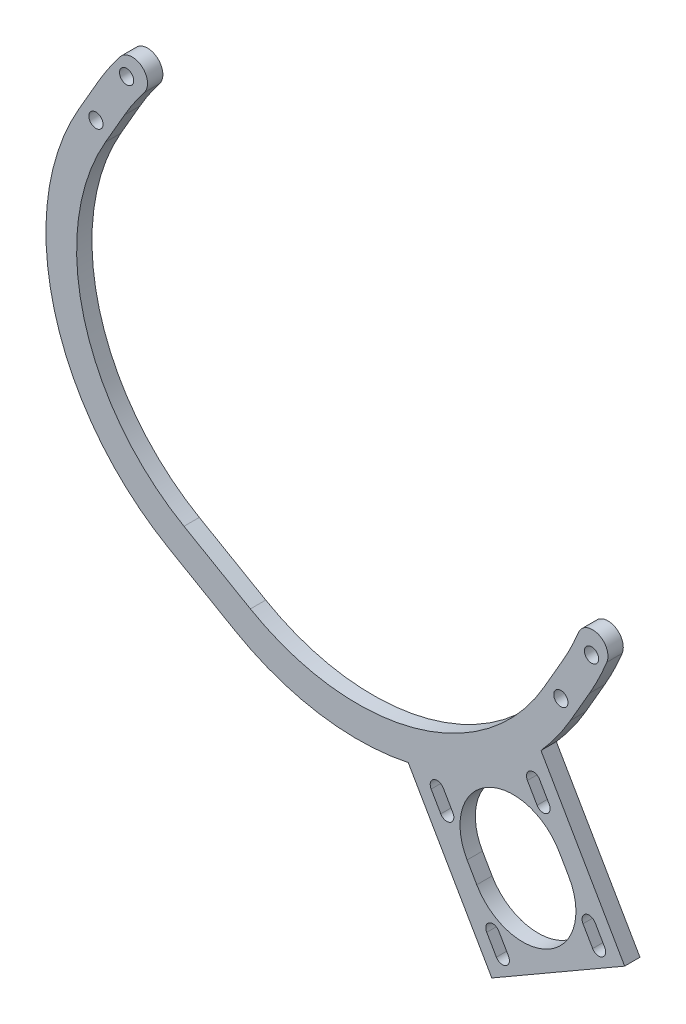
SolidWorks part; units mm, degrees
ref_plane "Front Plane" through (0, 0, 0) normal (0, 0, 1) x (1, 0, 0)
ref_plane "Top Plane" through (0, 0, 0) normal (0, 1, 0) x (1, 0, 0)
ref_plane "Right Plane" through (0, 0, 0) normal (1, 0, 0) x (0, 0, -1)
sketch "Sketch1" plane through (0, 0, -14.157) normal (0, 0, -1) x (-1, 0, 0)
  line L0 (-49.1723, -34.5021) -> (-53.1411, -27.628)
  line L1 (-2.2729, 1.7407) -> (29.3872, -53.0962) construction
  line L2 (20.2218, -53.0962) -> (27.0959, -49.1274)
  line L3 (33.9699, -45.1587) -> (20.2218, -53.0962) construction
  line L4 (17.0468, -47.5969) -> (23.9209, -43.6282)
  line L5 (-43.6731, -31.3271) -> (-47.6418, -24.453)
  line L6 (47.0648, 21.0604) -> (43.096, 27.9345)
  line L7 (30.7949, -39.6594) -> (23.9209, -43.6282)
  line L8 (33.9699, -45.1587) -> (27.0959, -49.1274)
  line L9 (52.564, 24.2354) -> (48.5953, 31.1095)
  arc A0 (-53.1411, -27.628) -> (-56.7299, -20.2712) centre (-2.2729, 1.7407) cw
  arc A3 (-61.0104, 1.7407) -> (-53.1411, -27.628) centre (-2.2729, 1.7407) ccw construction
  circle A4 centre (-53.5664, -20.5413) radius 1.1303 construction
  arc A5 (-49.1723, -34.5021) -> (20.2218, -53.0962) centre (-5.1782, -9.1021) ccw
  arc A6 (-43.6731, -31.3271) -> (17.0468, -47.5969) centre (-5.1782, -9.1021) ccw
  arc A7 (-47.6418, -24.453) -> (-50.8427, -17.8916) centre (-2.2729, 1.7407) cw
  arc A8 (-56.7299, -20.2712) -> (-50.8427, -17.8916) centre (-53.7863, -19.0814) cw
  arc A9 (44.0185, 37.8959) -> (39.014, 33.9872) centre (41.5163, 35.9416) ccw
  arc A10 (43.096, 27.9345) -> (39.014, 33.9872) centre (-2.2729, 1.7407) ccw
  arc A11 (47.0648, 21.0604) -> (30.7949, -39.6594) centre (8.5699, -1.1646) cw
  arc A12 (52.564, 24.2354) -> (33.9699, -45.1587) centre (8.5699, -1.1646) cw
  arc A13 (48.5953, 31.1095) -> (44.0185, 37.8959) centre (-2.2729, 1.7407) ccw
  dimension "D1" = 3.175
  dimension "D2" = 6.35
extrude "Boss-Extrude1" add sketch "Sketch1" along normal blind 3.175
hole_wizard "#4 Clearance Hole1" positions "Sketch5" profile "Sketch4" hole size "#4" standard "Ansi Inch" end condition through all
sketch "Sketch5" plane through (0, 0, -17.332) normal (0, 0, -1) x (-1, 0, 0)
  circle A1 centre (-53.5664, -20.5413) radius 1.1303 construction
  circle A2 centre (49.0206, 24.0227) radius 1.1303 construction
  point P0 (-53.5664, -20.5413)
  point P5 (-47.2164, -31.5398)
  point P8 (42.6706, 35.0212)
  point P11 (49.0206, 24.0227)
sketch "Sketch4" plane through (53.5664, -20.5413, -17.332) normal (1, 0, 0) x (0, 1, 0)
  line L0 (0, 0) -> (0, 3.175)
  line L1 (0, 3.175) -> (1.4732, 3.175)
  line L2 (1.4732, 3.175) -> (1.4732, 0)
  line L3 (-13.9608, 3.175) -> (-39.3608, 3.175) construction
  line L5 (1.4732, 0) -> (0, 0)
  line L11 (0, -6.35) -> (0, 107.95) construction
  dimension "Thru Hole Dia." = 2.9464
  dimension "Thru Hole Depth" = 3.175
ref_plane "Plane1" through (0, -58.42, 0) normal (0, 1, 0) x (-1, 0, 0)
ref_plane "Plane2" through (0, 0, -14.157) normal (0, 0, 1) x (1, 0, 0)
ref_axis "Axis2" through (-65.1865, 0, -14.157) along (1, 0, 0)
ref_axis "Axis3" through (0, 0, -25.4783) along (0, 0, 1)
ref_point "Point1"
ref_axis "Axis4" through (0, -70.9509, -14.157) along (0, 1, 0)
sketch "Sketch6" plane through (0, 0, -14.157) normal (0, 0, 1) x (1, 0, 0)
  line L0 (0, 0) -> (37.0667, -64.2014) construction
  line L1 (0, -70.9509) -> (0, 0.8498) construction
  line L10 (60.4207, -72.9016) -> (32.9243, -88.7766)
  line L15 (60.4207, -72.9016) -> (41.209, -39.6261)
  line L16 (32.9243, -88.7766) -> (13.7127, -55.5011)
  line L17 (41.209, -39.6261) -> (13.7127, -55.5011)
  line L18 (60.4207, -72.9016) -> (13.7127, -55.5011) construction
  line L19 (32.9243, -88.7766) -> (41.209, -39.6261) construction
  line L20 (37.338, -64.6713) -> (39.3319, -68.1248) construction
  line L21 (46.8627, -59.1722) -> (48.8566, -62.6257)
  line L22 (27.8133, -70.1704) -> (29.8072, -73.6239)
  line L23 (20.7526, -58.957) -> (37.8813, -88.6247) construction
  line L24 (35.1203, -83.8426) -> (33.1264, -80.3891) construction
  line L25 (57.5015, -76.5831) -> (40.1032, -46.4484) construction
  line L26 (33.8665, -84.5665) -> (31.8726, -81.113)
  line L27 (36.3742, -83.1187) -> (34.3803, -79.6652)
  line L28 (21.6202, -60.4598) -> (23.6141, -63.9133) construction
  line L29 (22.8741, -59.7359) -> (24.868, -63.1894)
  line L30 (20.3664, -61.1837) -> (22.3603, -64.6372)
  line L31 (41.5496, -48.9536) -> (43.5435, -52.4071) construction
  line L32 (42.8034, -48.2297) -> (44.7973, -51.6832)
  line L33 (40.2957, -49.6775) -> (42.2896, -53.131)
  line L34 (53.0558, -68.8829) -> (55.0497, -72.3364) construction
  line L35 (54.3096, -68.159) -> (56.3035, -71.6125)
  line L36 (51.8019, -69.6068) -> (53.7958, -73.0603)
  line L37 (23.6141, -63.9133) -> (43.5435, -52.4071) construction
  arc A0 (33.8665, -84.5665) -> (36.3742, -83.1187) centre (35.1203, -83.8426) ccw
  arc A1 (34.3803, -79.6652) -> (31.8726, -81.113) centre (33.1264, -80.3891) ccw
  arc A2 (-17.0468, -47.5969) -> (43.6731, -31.3271) centre (5.1782, -9.1021) ccw construction
  arc A3 (46.8627, -59.1722) -> (27.8133, -70.1704) centre (37.338, -64.6713) ccw
  arc A4 (29.8072, -73.6239) -> (48.8566, -62.6257) centre (39.3319, -68.1248) ccw
  arc A5 (22.8741, -59.7359) -> (20.3664, -61.1837) centre (21.6202, -60.4598) ccw
  arc A6 (22.3603, -64.6372) -> (24.868, -63.1894) centre (23.6141, -63.9133) ccw
  arc A7 (42.8034, -48.2297) -> (40.2957, -49.6775) centre (41.5496, -48.9536) ccw
  arc A8 (42.2896, -53.131) -> (44.7973, -51.6832) centre (43.5435, -52.4071) ccw
  arc A9 (54.3096, -68.159) -> (51.8019, -69.6068) centre (53.0558, -68.8829) ccw
  arc A10 (53.7958, -73.0603) -> (56.3035, -71.6125) centre (55.0497, -72.3364) ccw
  point P3 (38.3349, -66.3981)
  point P25 (34.1234, -82.1158)
  point P30 (22.6172, -62.1865)
  point P37 (42.5465, -50.6803)
  point P44 (54.0527, -70.6096)
  dimension "D4" = 10.9982
  dimension "D5" = 11.5062
  dimension "D8" = 1.4478
  dimension "D9" = 23.0124
  dimension "D14" = 1.4478
  dimension "D15" = 1.4478
  dimension "D16" = 1.4478
  dimension "D19" = 3.9878
  dimension "D1" = 30
  dimension "D2" = 93.345
  dimension "D3" = 31.75
  dimension "D6" = 11.5062
  dimension "D7" = 3.9878
  dimension "D10" = 23.0124
  dimension "D11" = 3.9878
  dimension "D12" = 3.9878
  dimension "D13" = 3.9878
  dimension "D17" = 3.175
  dimension "D18" = 3.175
  dimension "D20" = 11.5062
extrude "Boss-Extrude2" add sketch "Sketch6" against normal up to surface (3.175 mm away) up to face at (52.0932, -20.5413, -17.332)
